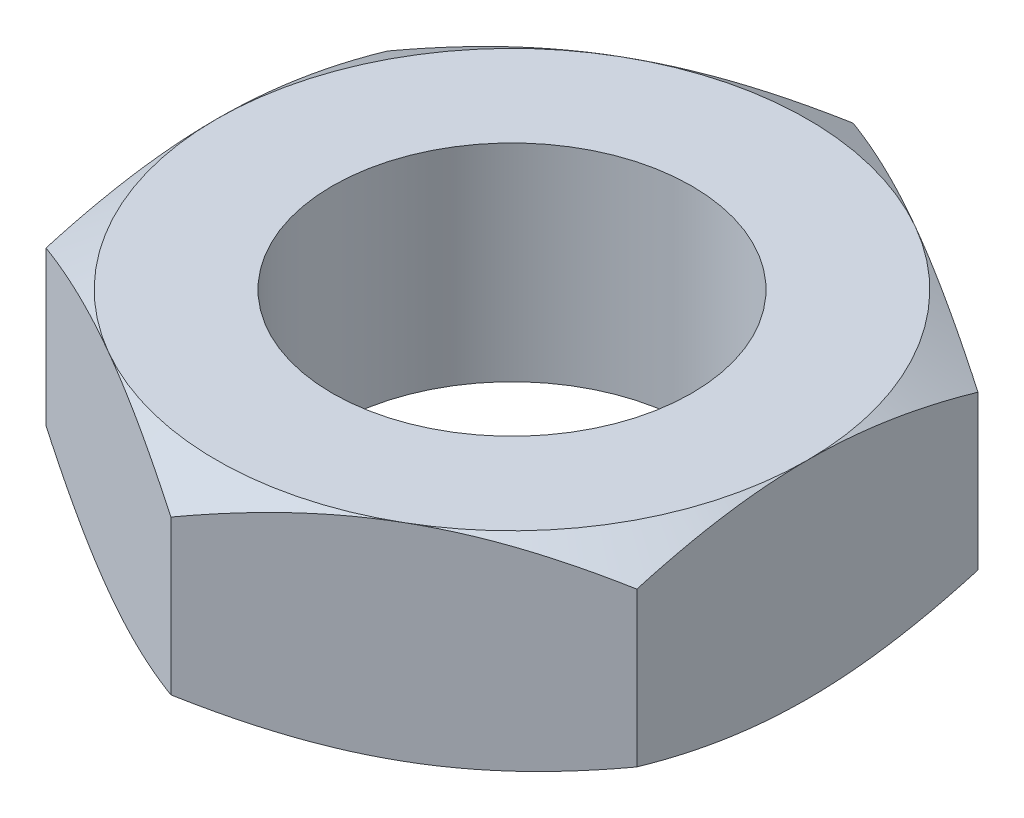
SolidWorks part; units mm, degrees
ref_plane "Front Plane" through (0, 0, 0) normal (0, 0, 1) x (1, 0, 0)
ref_plane "Top Plane" through (0, 0, 0) normal (0, 1, 0) x (1, 0, 0)
ref_plane "Right Plane" through (0, 0, 0) normal (1, 0, 0) x (0, 0, -1)
sketch "Sketch1" plane through (0, 0, 0) normal (0, 1, 0) x (1, 0, 0)
  line L1 (-3.9688, 2.2914) -> (-3.9688, -2.2914)
  line L2 (-3.9688, -2.2914) -> (0, -4.5827)
  line L3 (0, -4.5827) -> (3.9687, -2.2914)
  line L4 (3.9687, -2.2914) -> (3.9688, 2.2914)
  line L5 (3.9688, 2.2914) -> (0, 4.5827)
  line L6 (0, 4.5827) -> (-3.9688, 2.2914)
  circle A0 centre (0, 0) radius 3.9688 construction
  circle A1 centre (0, 0) radius 2.413
  dimension "Thread Size" = 4.826
  dimension "Hex" = 7.9375
extrude "Boss-Extrude1" add sketch "Sketch1" along normal mid plane 2.7781
sketch "Sketch2" plane through (0, 1.3891, 0) normal (0, 1, 0) x (1, 0, 0)
  circle A0 centre (0, 0) radius 2.413 construction
  circle A1 centre (0, 0) radius 2.413
curve "Helix/Spiral1" [suppressed] pitch 1.0583 height 3.8365 turns 3.625 parameters "Pitch"=1.0583
sketch "Sketch3" plane through (0, 0, 0) normal (1, 0, 0) x (0, 0, -1)
  line L0 (1.7256, 1.9182) -> (2.413, 2.3151)
  line L1 (2.413, 2.3151) -> (2.413, 1.3891)
  line L2 (2.413, 1.3891) -> (1.7256, 1.7859)
  line L3 (1.7256, 1.7859) -> (1.7256, 1.9182)
  line L4 (2.0693, 2.1167) -> (2.0693, 1.5875) construction
  line L5 (1.7256, 1.8521) -> (2.413, 1.8521) construction
  line L6 (2.413, 1.3891) -> (-2.413, 1.3891) construction
  dimension "D1" = 60
  dimension "D2" = 0.1323
  dimension "D3" = 0.5292
sweep "Sweep1" [suppressed] add profiles "Sketch3" path "Helix/Spiral1"
sketch "Sketch4" plane through (0, 1.3891, 0) normal (0, 1, 0) x (1, 0, 0)
  circle A1 centre (0, 0) radius 2.413
  circle A2 centre (0, 0) radius 2.413
  dimension "D1" = 0
sketch "Sketch5" plane through (0, 1.3891, 0) normal (0, 1, 0) x (1, 0, 0)
  circle A0 centre (0, 0) radius 3.9688 construction
  circle A1 centre (0, 0) radius 3.9688
extrude "Cut-Extrude2" cut sketch "Sketch5" against normal through all draft 60 flip side to cut
mirror "Mirror1" about plane through (0, 0, 0) normal (0, 1, 0) of "Cut-Extrude2"
equation "\"D2@Sketch3\" = \"Pitch@Helix/Spiral1\"*.125"
equation "\"D3@Sketch3\" = \"Pitch@Helix/Spiral1\"*.5"
equation "\"D3@Helix/Spiral1\" = \"Height@Boss-Extrude1\"+\"Pitch@Helix/Spiral1\""
